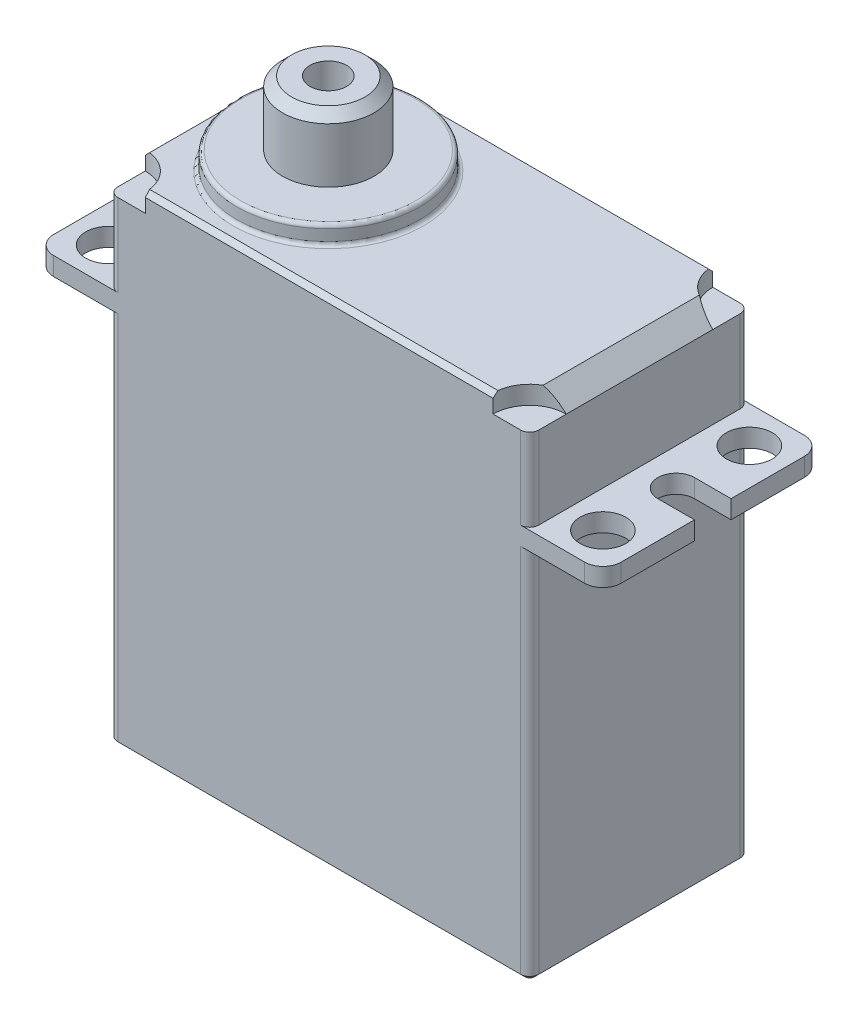
SolidWorks part; units mm, degrees
material "1060-O (SS)"
ref_plane "Front Plane" through (0, 0, 0) normal (0, 0, 1) x (1, 0, 0)
ref_plane "Top Plane" through (0, 0, 0) normal (0, 1, 0) x (1, 0, 0)
ref_plane "Right Plane" through (0, 0, 0) normal (1, 0, 0) x (0, 0, -1)
sketch "Sketch1" plane through (0, 0, 0) normal (0, 1, 0) x (1, 0, 0)
  line L1 (-11.0424, 5.8263) -> (11.9576, 5.8263)
  line L2 (-11.0424, 5.8263) -> (-11.0424, -6.1737)
  line L3 (-11.0424, -6.1737) -> (11.9576, -6.1737)
  line L4 (11.9576, 5.8263) -> (11.9576, -6.1737)
  dimension "D1" = 23
  dimension "D2" = 12
extrude "Boss-Extrude1" add sketch "Sketch1" along normal blind 27
sketch "Sketch2" plane through (0, 27, 0) normal (0, 1, 0) x (1, 0, 0)
  line L0 (-11.0424, -0.1737) -> (11.9576, -0.1737) construction
  line L1 (-11.0424, 5.8263) -> (-11.0424, -6.1737) construction
  line L2 (11.9576, -6.1737) -> (11.9576, 5.8263) construction
  circle A0 centre (-5.0424, -0.1737) radius 5
  point P6 (-5.0424, -0.1737)
  dimension "D2" = 10
  dimension "D1" = 6
extrude "Boss-Extrude2" add sketch "Sketch2" along normal blind 1
fillet "Fillet1" radius 0.2 2 edges at (-5.0424, 27, 5.1737) (-5.0424, 28, 5.1737)
sketch "Sketch3" plane through (0, 28, 0) normal (0, 1, 0) x (1, 0, 0)
  circle A0 centre (-5.0424, -0.1737) radius 2.5
  point P0 (-5.0424, -0.1737)
extrude "Boss-Extrude3" add sketch "Sketch3" along normal blind 3.5
chamfer "Chamfer1" distance 0.5 angle 45 1 edges at (-5.0424, 31.5, 2.6737)
sketch "Sketch4" plane through (0, 31.5, 0) normal (0, 1, 0) x (1, 0, 0)
  circle A0 centre (-5.0424, -0.1737) radius 1
extrude "Cut-Extrude1" cut sketch "Sketch4" against normal blind 3.5
ref_plane "Plane1" through (0, 21.5, 0) normal (0, 1, 0) x (1, 0, 0)
sketch "Sketch5" plane through (0, 21.5, 0) normal (0, 1, 0) x (1, 0, 0)
  line L0 (-11.0424, 5.8263) -> (-11.0424, -6.1737) construction
  line L1 (0.4576, 5.8263) -> (0.4576, -6.1737) construction
  line L2 (-15.0424, 4.8263) -> (-15.0424, 0.8263)
  line L3 (11.9576, 5.8263) -> (-11.0424, 5.8263) construction
  line L4 (-11.0424, -6.1737) -> (11.9576, -6.1737) construction
  line L5 (-14.0424, 5.8263) -> (14.9576, 5.8263)
  line L6 (-14.0424, -6.1737) -> (14.9576, -6.1737)
  line L7 (-15.0424, -0.1737) -> (-11.0424, -0.1737) construction
  line L8 (-15.0424, 0.8263) -> (-13.0424, 0.8263)
  line L9 (15.9576, -0.1737) -> (11.9576, -0.1737) construction
  line L10 (-15.0424, -1.1737) -> (-13.0424, -1.1737)
  line L11 (-15.0424, -1.1737) -> (-15.0424, -5.1737)
  line L12 (15.9576, -1.1737) -> (15.9576, -5.1737)
  line L13 (15.9576, -1.1737) -> (13.9576, -1.1737)
  line L14 (15.9576, 0.8263) -> (13.9576, 0.8263)
  line L15 (15.9576, 4.8263) -> (15.9576, 0.8263)
  arc A0 (-15.0424, -5.1737) -> (-14.0424, -6.1737) centre (-14.0424, -5.1737) ccw
  arc A1 (-15.0424, 4.8263) -> (-14.0424, 5.8263) centre (-14.0424, 4.8263) cw
  arc A2 (-13.0424, -1.1737) -> (-13.0424, 0.8263) centre (-13.0424, -0.1737) ccw
  circle A3 centre (-13.0424, 3.8263) radius 1.25
  circle A4 centre (-13.0424, -4.1737) radius 1.25
  circle A5 centre (13.9576, -4.1737) radius 1.25
  circle A6 centre (13.9576, 3.8263) radius 1.25
  arc A7 (13.9576, -1.1737) -> (13.9576, 0.8263) centre (13.9576, -0.1737) cw
  arc A8 (15.9576, 4.8263) -> (14.9576, 5.8263) centre (14.9576, 4.8263) ccw
  arc A9 (15.9576, -5.1737) -> (14.9576, -6.1737) centre (14.9576, -5.1737) cw
  point P20 (-12.0424, -0.1737)
  point P43 (12.9576, -0.1737)
  dimension "D2" = 1
  dimension "D3" = 2
  dimension "D1" = 4
  dimension "D4" = 1
  dimension "D5" = 2
extrude "Boss-Extrude4" add sketch "Sketch5" against normal blind 1
fillet "Fillet2" radius 0.5 4 edges at (11.9576, 24.25, -5.8263) (11.9576, 24.25, 6.1737) (-11.0424, 24.25, -5.8263) (-11.0424, 24.25, 6.1737)
sketch "Sketch6" plane through (0, 27, 0) normal (0, 1, 0) x (1, 0, 0)
  line L0 (0.4576, 5.8263) -> (0.4576, -6.1737) construction
  line L1 (11.4576, 5.8263) -> (-10.5424, 5.8263) construction
  line L2 (-10.5424, -6.1737) -> (11.4576, -6.1737) construction
  line L3 (11.9576, -0.1737) -> (-11.0424, -0.1737) construction
  line L4 (11.9576, -5.6737) -> (11.9576, 5.3263) construction
  line L5 (-11.0424, 5.3263) -> (-11.0424, -5.6737) construction
  line L6 (-10.317, 5.8263) -> (-11.0424, 5.8263) construction
  line L7 (-11.0424, 4.91) -> (-11.0424, 5.8263) construction
  circle A0 centre (-11.0424, 5.8263) radius 2
  circle A1 centre (11.9576, 5.8263) radius 2
  circle A2 centre (11.9576, -6.1737) radius 2
  circle A3 centre (-11.0424, -6.1737) radius 2
extrude "Cut-Extrude2" cut sketch "Sketch6" against normal blind 1
chamfer "Chamfer2" distance 1 angle 45 1 edges at (11.9576, 27, 0.1737)
fillet "Fillet3" radius 0.5 4 edges at (-11.0424, 10.25, 6.1737) (11.9576, 10.25, -5.8263) (11.9576, 10.25, 6.1737) (-11.0424, 10.25, -5.8263)
chamfer "Chamfer3" distance 0.25 angle 45 11 edges at (0.4576, 0, -5.8263) (-11.0424, 0, 0.1737) (11.9576, 0, 0.1737) (0.4576, 0, 6.1737) (0.4576, 27, -5.8263) (0.4576, 27, 6.1737) (-11.0424, 27, 0.1737) (-10.896, 0, -5.6798) (11.8111, 0, -5.6798) (-10.896, 0, 6.0273) (11.8111, 0, 6.0273)
